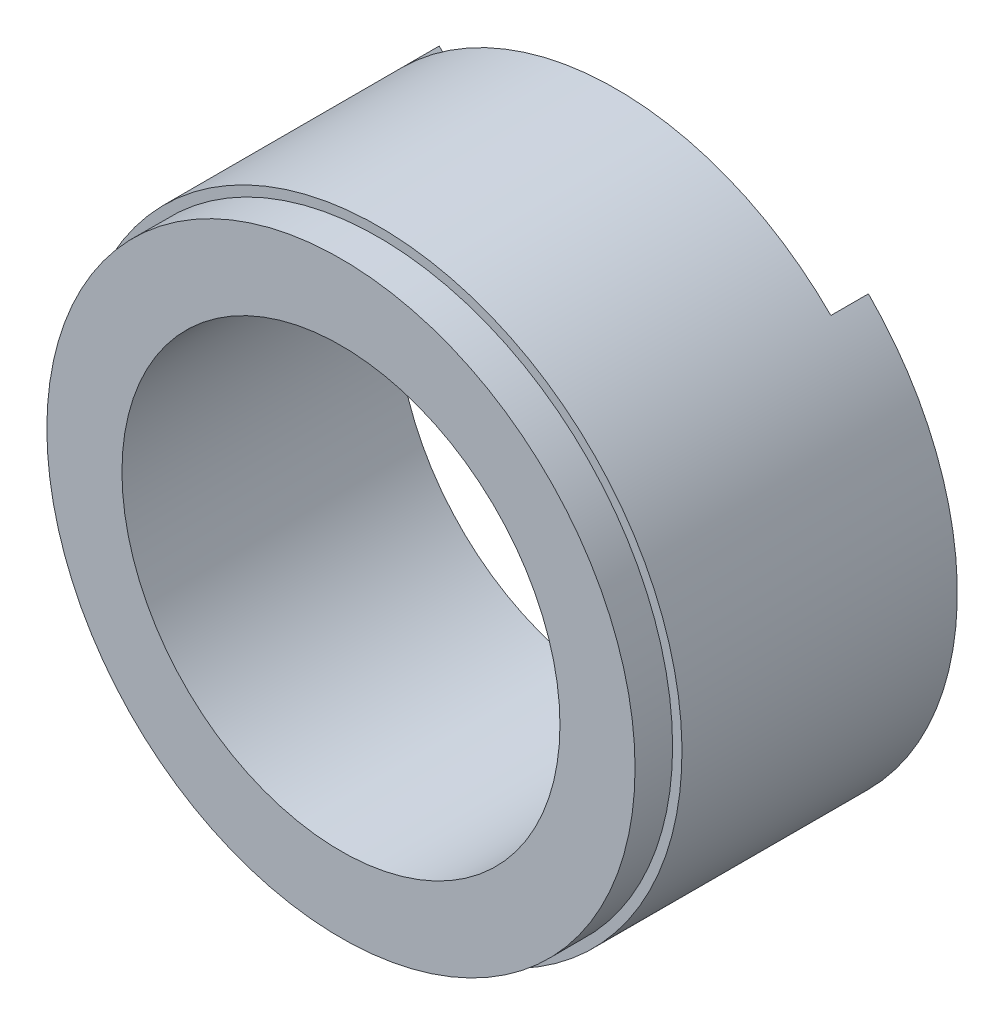
SolidWorks part; units mm, degrees
ref_plane "Plan de face" through (0, 0, 0) normal (0, 0, 1) x (1, 0, 0)
ref_plane "Plan de dessus" through (0, 0, 0) normal (0, 1, 0) x (1, 0, 0)
ref_plane "Plan de droite" through (0, 0, 0) normal (1, 0, 0) x (0, 0, -1)
sketch "Esquisse1" plane through (0, 0, 0) normal (0, 0, 1) x (1, 0, 0)
  circle A0 centre (0, 0) radius 48.5
  dimension "D1" = 97
extrude "Boss.-Extru.1" add sketch "Esquisse1" along normal blind 44
sketch "Esquisse2" plane through (0, 0, 44) normal (0, 0, 1) x (1, 0, 0)
  circle A0 centre (0, 0) radius 48.5
  circle A1 centre (0, 0) radius 47
  dimension "D1" = 94
extrude "Enlèv. mat.-Extru.1" cut sketch "Esquisse2" against normal blind 6
sketch "Esquisse3" plane through (0, 0, 44) normal (0, 0, 1) x (1, 0, 0)
  circle A0 centre (0, 0) radius 35
  dimension "D1" = 70
extrude "Enlèv. mat.-Extru.2" cut sketch "Esquisse3" against normal through all
sketch "Esquisse5" plane through (0, 0, 0) normal (0, 0, -1) x (-1, 0, 0)
  circle A0 centre (0, 0) radius 36.5
  circle A1 centre (0, 0) radius 45.5
  circle A2 centre (0, 0) radius 35 construction
  dimension "D1" = 9
  dimension "D2" = 1.5
extrude "Enlèv. mat.-Extru.3" cut sketch "Esquisse5" against normal blind 42
sketch "Esquisse6" plane through (0, 0, 0) normal (0, 0, -1) x (-1, 0, 0)
  line L5 (-10, -48.5543) -> (10, -48.5543)
  line L6 (-10, -48.5543) -> (-10, -44.3875)
  line L7 (-10, -44.3875) -> (10, -44.3875)
  line L8 (10, -48.5543) -> (10, -44.3875)
  circle A1 centre (0, 0) radius 45.5 construction
  dimension "D1" = 20
  dimension "D2" = 10
extrude "Enlèv. mat.-Extru.5" cut sketch "Esquisse6" against normal blind 42
sketch "Esquisse8" plane through (0, 0, 0) normal (0, 0, -1) x (-1, 0, 0)
  line L0 (48.5, 0) -> (-48.5, 0) construction
  line L1 (0, 0) -> (32.1734, -32.1734) construction
  line L2 (0, 0) -> (32.1734, 32.1734) construction
  line L3 (34.2947, 34.2947) -> (32.1734, 32.1734)
  line L4 (34.2947, -34.2947) -> (32.1734, -32.1734)
  line L5 (0, 0) -> (0, -36.5) construction
  line L6 (-34.2947, -34.2947) -> (-32.1734, -32.1734)
  line L7 (-34.2947, 34.2947) -> (-32.1734, 32.1734)
  circle A0 centre (0, 0) radius 48.5 construction
  circle A1 centre (0, 0) radius 45.5 construction
  arc A2 (32.1734, -32.1734) -> (32.1734, 32.1734) centre (0, 0) ccw
  arc A3 (34.2947, -34.2947) -> (34.2947, 34.2947) centre (0, 0) ccw
  circle A4 centre (0, 0) radius 36.5 construction
  arc A5 (-32.1734, -32.1734) -> (-32.1734, 32.1734) centre (0, 0) cw
  arc A6 (-34.2947, -34.2947) -> (-34.2947, 34.2947) centre (0, 0) cw
  arc M16 (10, -47.4579) -> (-10, -47.4579) centre (0, 0) ccw
  arc M18 (-10, -44.3875) -> (10, -44.3875) centre (0, 0) cw
  dimension "D1" = 45
  dimension "D2" = 45
extrude "Boss.-Extru.2" add sketch "Esquisse8" along normal blind 6 contours L4 L3 M16 M18 | A6 L7 A5 L6 region at (-47.7949, 0, 0)
